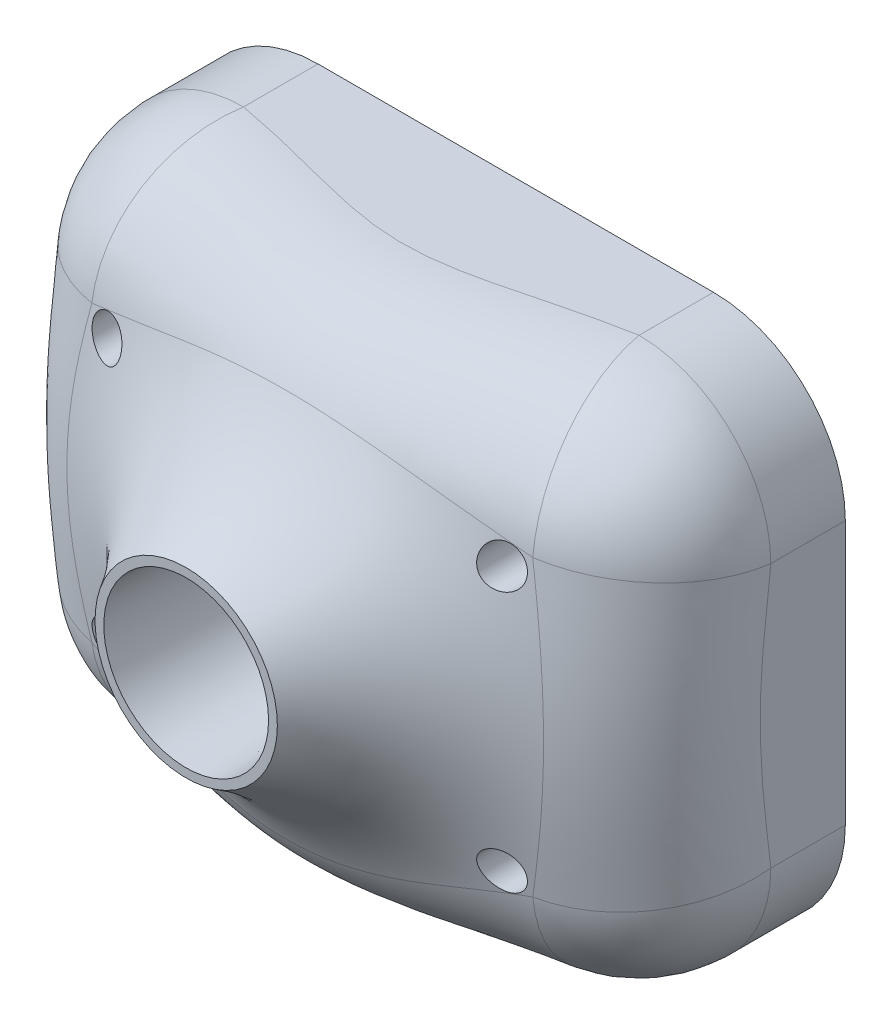
SolidWorks part; units mm, degrees
ref_plane "Front Plane" through (0, 0, 0) normal (0, 0, 1) x (1, 0, 0)
ref_plane "Top Plane" through (0, 0, 0) normal (0, 1, 0) x (1, 0, 0)
ref_plane "Right Plane" through (0, 0, 0) normal (1, 0, 0) x (0, 0, -1)
sketch "Sketch1" plane through (0, 0, 0) normal (0, 0, 1) x (1, 0, 0)
  line L5 (-25, -20) -> (25, -20)
  line L6 (-25, -20) -> (-25, 20)
  line L7 (-25, 20) -> (25, 20)
  line L8 (25, -20) -> (25, 20)
  line L9 (-25, -20) -> (25, 20) construction
  line L10 (-25, 20) -> (25, -20) construction
  point P4 (0, 0)
  dimension "D3" = 40
  dimension "D4" = 50
extrude "Boss-Extrude1" add sketch "Sketch1" along normal blind 15
sketch "Sketch2" plane through (0, 0, 15) normal (0, 0, 1) x (1, 0, 0)
  circle A0 centre (0, 0) radius 8.5
  dimension "D1" = 17
extrude "Boss-Extrude2" add sketch "Sketch2" along normal blind 10 draft 9 contours A0
sketch "Sketch3" plane through (0, 0, 25) normal (0, 0, 1) x (1, 0, 0)
  circle A0 centre (0, 0) radius 6.25
  dimension "D1" = 12.5
extrude "Cut-Extrude1" cut sketch "Sketch3" against normal blind 23 draft 2
fillet "Fillet1" radius 20 1 edges at (8.5, 0, 15)
fillet "Fillet2" radius 10 4 edges at (25, -20, 7.5) (-25, -20, 7.5) (25, 20, 7.5) (-25, 20, 7.5)
sketch "Sketch4" plane through (0, 0, 0) normal (0, 0, -1) x (-1, 0, 0)
  line L0 (0, 20) -> (0, -20) construction
  line L1 (-15, 20) -> (15, 20) construction
  line L2 (15, -20) -> (-15, -20) construction
  line L3 (-25, 0) -> (25, 0) construction
  line L4 (-25, -10) -> (-25, 10) construction
  line L5 (25, 10) -> (25, -10) construction
  circle A4 centre (-15, 10) radius 1.5
  circle A5 centre (15, 10) radius 1.5
  circle A6 centre (15, -10) radius 1.5
  circle A7 centre (-15, -10) radius 1.5
  dimension "D1" = 3
extrude "Cut-Extrude2" cut sketch "Sketch4" against normal blind 30
fillet "Fillet3" radius 10 8 edges at (25, 0, 15) (-25, 0, 15) (-1.5717, 20, 15.4406) (14.345, 20, 15) (22.0711, 17.0711, 15) (1.5717, -20, 15.4406) (-22.0711, 17.0711, 15) (-14.345, 20, 15)
